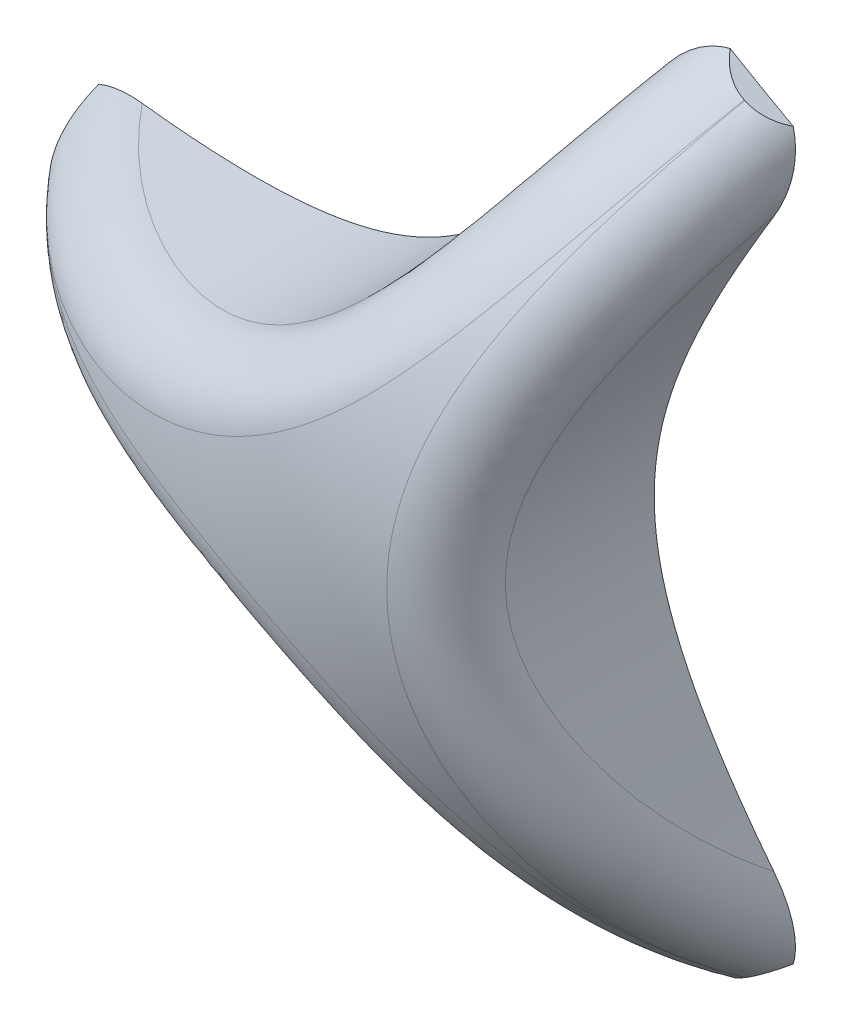
SolidWorks part; units mm, degrees
ref_plane "Front Plane" through (0, 0, 0) normal (0, 0, 1) x (1, 0, 0)
ref_plane "Top Plane" through (0, 0, 0) normal (0, 1, 0) x (1, 0, 0)
ref_plane "Right Plane" through (0, 0, 0) normal (1, 0, 0) x (0, 0, -1)
sketch "Sketch1" plane through (0, 0, 0) normal (0, 0, 1) x (1, 0, 0)
  line L0 (6.299, 7.9103) -> (3.701, 9.4103)
  line L1 (-10, 1.5) -> (0, 1.5) construction
  line L2 (-10, 1.5) -> (-10, -1.5)
  line L3 (-10, -1.5) -> (0, -1.5) construction
  line L4 (0, 1.5) -> (0, -1.5) construction
  line L5 (6.299, 7.9103) -> (1.299, -0.75) construction
  line L6 (3.701, 9.4103) -> (-1.299, 0.75) construction
  line L7 (1.299, -0.75) -> (-1.299, 0.75) construction
  line L8 (3.701, -9.4103) -> (6.299, -7.9103)
  line L9 (3.701, -9.4103) -> (-1.299, -0.75) construction
  line L10 (6.299, -7.9103) -> (1.299, 0.75) construction
  line L11 (-1.299, -0.75) -> (1.299, 0.75) construction
  spline S0 degree 3 poles (-10, 1.5) (-1.6667, 1.5) (-0.4657, 2.1934) (3.701, 9.4103) knots 0 0 0 0 1 1 1 1
  spline S1 degree 3 poles (6.299, 7.9103) (2.1324, 0.6934) (2.1324, -0.6934) (6.299, -7.9103) knots 0 0 0 0 1 1 1 1
  spline S2 degree 3 poles (3.701, -9.4103) (-0.4657, -2.1934) (-1.6667, -1.5) (-10, -1.5) knots 0 0 0 0 1 1 1 1
  point P4 (0, 0)
  point P16 (0, 0)
  point P21 (0, 0)
  dimension "D4" = 25
  dimension "D5" = 25
  dimension "D1" = 3
  dimension "D2" = 10
  dimension "D3" = 3
extrude "Boss-Extrude1" add sketch "Sketch1" along normal mid plane 15 from offset 75
sketch "Sketch2" plane through (0, 0, 0) normal (0, 1, 0) x (1, 0, 0)
  line L0 (-0.385, -71.5435) -> (-0.385, -76.5435)
  arc A0 (-10.8999, -70.8028) -> (-0.385, -71.5435) centre (-0.385, 3.4565) ccw
  arc A1 (-10.8999, -70.8028) -> (-0.385, -76.5435) centre (-0.385, -64.0435) ccw
  dimension "D1" = 25
  dimension "150" = 150
  dimension "D2" = 5
revolve "Revolve1" add sketch "Sketch2" angle 360 about L0
combine bodies "Combine1" operation type common bodies to combine 101 106
fillet "Fillet1" radius 1.5 3 edges at (-1.315, 2.9147, 76.1633) (3.1934, -0.5083, 76.0096) (-2.2542, -2.4116, 76.1654)
sketch "Sketch3" plane through (0, 0, 0) normal (0, 0, 1) x (1, 0, 0)
  line L0 (0, 0) -> (12.4409, 7.1828) construction
  line L1 (5.0454, -8.634) -> (5.7151, -8.2474) construction
